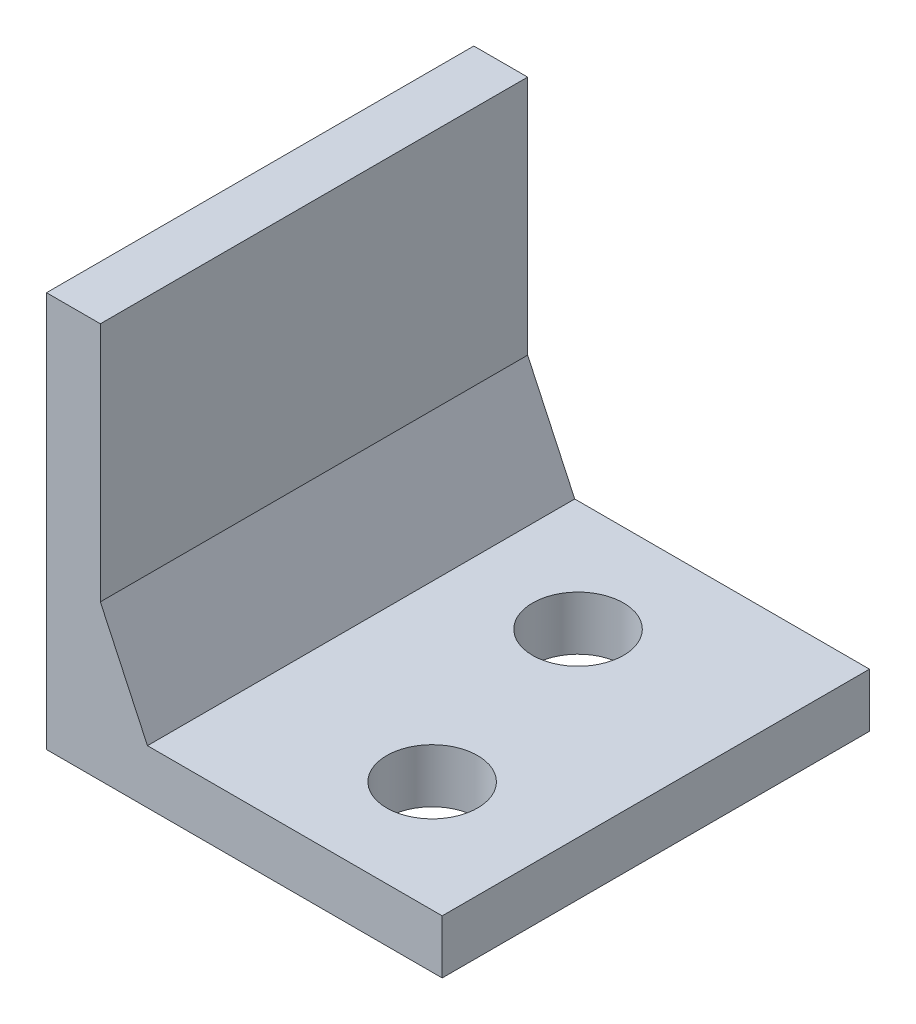
SolidWorks part; units mm, degrees
material "ABS"
ref_plane "Front Plane" through (0, 0, 0) normal (0, 0, 1) x (1, 0, 0)
ref_plane "Top Plane" through (0, 0, 0) normal (0, 1, 0) x (1, 0, 0)
ref_plane "Right Plane" through (0, 0, 0) normal (1, 0, 0) x (0, 0, -1)
sketch "Sketch1" plane through (0, 0, 0) normal (0, 0, 1) x (1, 0, 0)
  line L0 (0, 0) -> (0, 29.4)
  line L1 (0, 29.4) -> (4, 29.4)
  line L2 (4, 29.4) -> (4, 4)
  line L3 (4, 4) -> (29.4, 4)
  line L4 (29.4, 4) -> (29.4, 0)
  line L5 (29.4, 0) -> (0, 0)
  dimension "D1" = 4
  dimension "D2" = 25.4
  dimension "D3" = 25.4
extrude "Boss-Extrude1" add sketch "Sketch1" along normal blind 31.75
hole_wizard "1/4 Clearance Hole1" positions "Sketch2" profile "Sketch3" hole size "1/4" standard "ANSI Inch" end condition through all
sketch "Sketch2" plane through (0, 4, 0) normal (0, 1, 0) x (1, 0, 0)
  line L0 (4, -31.75) -> (4, 0) construction
  line L1 (29.4, -31.75) -> (29.4, 0) construction
  point P0 (20.4, -23.495)
  point P2 (16, -8.255)
  point P10 (29.4, -15.875)
  dimension "D1" = 16.4
  dimension "D2" = 12
  dimension "D3" = 15.24
  dimension "D4" = 7.62
sketch "Sketch3" plane through (20.4, 4, 23.495) normal (1, 0, 0) x (0, 0, 1)
  line L0 (0, 0) -> (0, 4)
  line L1 (0, 4) -> (3.3782, 4)
  line L2 (3.3782, 4) -> (3.3782, 0)
  line L5 (3.3782, 0) -> (0, 0)
  line L11 (0, -6.35) -> (0, 107.95) construction
  dimension "Thru Hole Dia." = 6.7564
  dimension "Thru Hole Depth" = 4
chamfer "Chamfer1" distance 3.5 angle 65 1 edges at (4, 4, 15.875) first distance on face at (20.4, 4, 26.8732)
equation "\"D4@Sketch2\"=\"D3@Sketch2\"/2"
